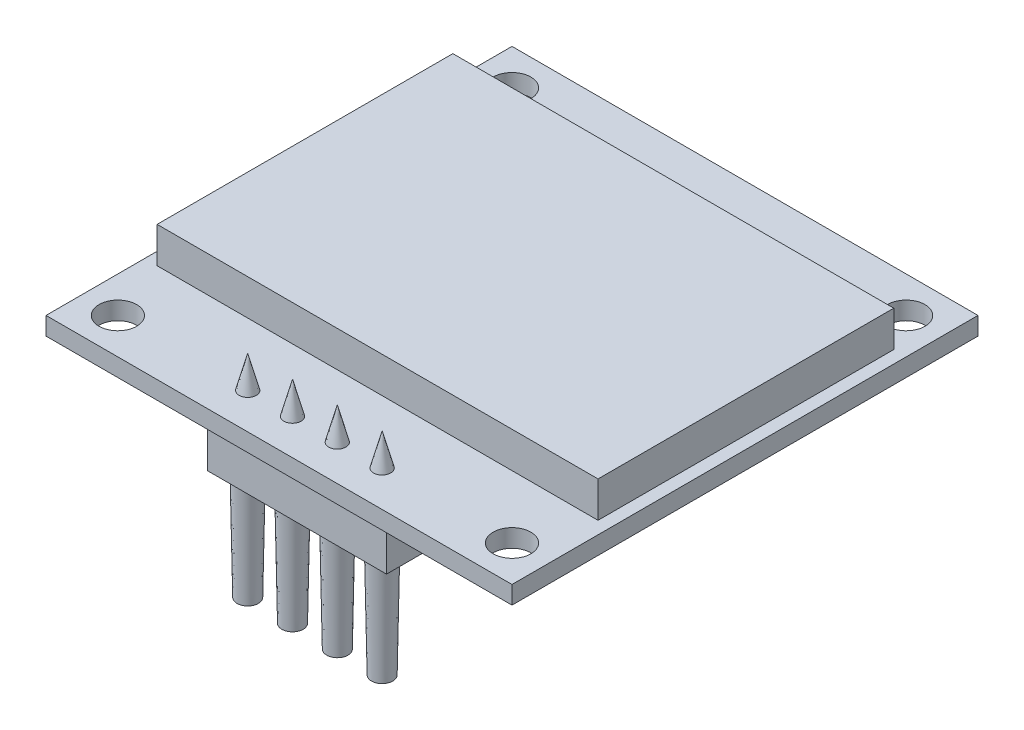
SolidWorks part; units mm, degrees
ref_plane "Piano frontale" through (0, 0, 0) normal (0, 0, 1) x (1, 0, 0)
ref_plane "Piano superiore" through (0, 0, 0) normal (0, 1, 0) x (1, 0, 0)
ref_plane "Piano destro" through (0, 0, 0) normal (1, 0, 0) x (0, 0, -1)
sketch "Schizzo1" plane through (0, 0, 0) normal (0, 1, 0) x (1, 0, 0)
  line L0 (-3.75, -10.9955) -> (3.75, -10.9955) construction
  line L1 (-13, 13) -> (13, 13)
  line L2 (-13, 13) -> (-13, -13)
  line L3 (-13, -13) -> (13, -13)
  line L4 (13, 13) -> (13, -13)
  line L5 (-13, 13) -> (13, -13) construction
  line L6 (-13, -13) -> (13, 13) construction
  line L7 (-12.3, 9) -> (12.3, 9)
  line L8 (-12.3, 9) -> (-12.3, -7.5)
  line L9 (-12.3, -7.5) -> (12.3, -7.5)
  line L10 (12.3, 9) -> (12.3, -7.5)
  line L11 (-12.3, 9) -> (12.3, -7.5) construction
  line L12 (-12.3, -7.5) -> (12.3, 9) construction
  circle A0 centre (10.9955, 10.9955) radius 1.05
  circle A1 centre (10.9955, -10.9955) radius 1.05
  circle A2 centre (-10.9955, -10.9955) radius 1.05
  circle A3 centre (-10.9955, 10.9955) radius 1.05
  circle A4 centre (-3.75, -10.9955) radius 0.75
  circle A5 centre (-1.25, -10.9955) radius 0.75
  circle A6 centre (1.25, -10.9955) radius 0.75
  circle A7 centre (3.75, -10.9955) radius 0.75
  point P0 (0, 0)
  point P8 (0, 0.75)
  point P17 (0, 0)
  point P20 (0, -10.9955)
  dimension "D3" = 2.1
  dimension "D5" = 4
  dimension "D9" = 4
  dimension "D1" = 26
  dimension "D2" = 26
  dimension "D4" = 15.55
  dimension "D6" = 24.6
  dimension "D7" = 16.5
  dimension "D8" = 4
  dimension "D10" = 10.9955
extrude "Estrusione-Estrusione1" add sketch "Schizzo1" along normal blind 1 contours L2 L3 L4 L1 | A2 | A3 | A0 | A1
extrude "Estrusione-Estrusione2" add sketch "Schizzo1<3>" along normal blind 3 separate body contours L9 L10 L7 L8
sketch "Schizzo1<3>" plane through (0, 0, 0) normal (0, 1, 0) x (1, 0, 0) same geometry as "Schizzo1"
extrude "Estrusione-Estrusione3" add sketch "Schizzo1<4>" along normal blind 3 draft 15 separate body contours A4 | A5 | A6 | A7
sketch "Schizzo1<4>" plane through (0, 0, 0) normal (0, 1, 0) x (1, 0, 0) same geometry as "Schizzo1"
sketch "Schizzo3" plane through (0, 0, 0) normal (0, 1, 0) x (1, 0, 0)
  line L1 (-5, -10) -> (5, -10)
  line L2 (-5, -10) -> (-5, -12)
  line L3 (-5, -12) -> (5, -12)
  line L4 (5, -10) -> (5, -12)
  line L5 (-5, -10) -> (5, -12) construction
  line L6 (-5, -12) -> (5, -10) construction
  point P0 (0, -11)
  point P5 (0, 0)
  point P7 (0, 0)
  point P8 (0, 0)
  point P9 (0, 0)
  dimension "D1" = 10
  dimension "D2" = 2
  dimension "D3" = 11
extrude "Estrusione-Estrusione4" add sketch "Schizzo3" against normal blind 3 separate body
extrude "Estrusione-Estrusione5" add sketch "Schizzo1<5>" against normal blind 9 draft 1 separate body contours A4 | A5 | A6 | A7
sketch "Schizzo1<5>" plane through (0, 0, 0) normal (0, 1, 0) x (1, 0, 0) same geometry as "Schizzo1"
